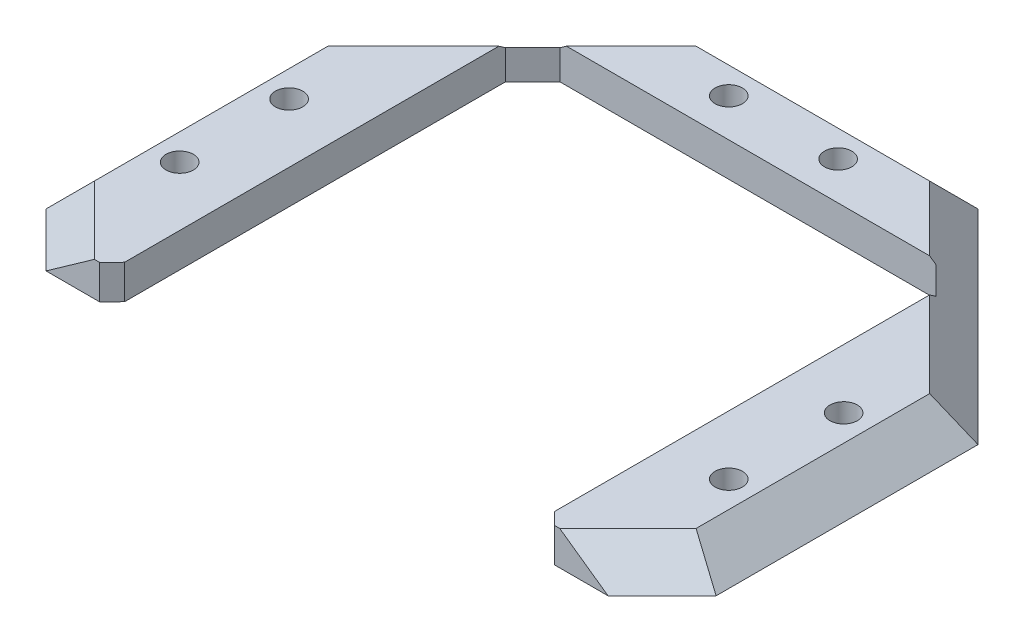
SolidWorks part; units mm, degrees
ref_plane "Front Plane" through (0, 0, 0) normal (0, 0, 1) x (1, 0, 0)
ref_plane "Top Plane" through (0, 0, 0) normal (0, 1, 0) x (1, 0, 0)
ref_plane "Right Plane" through (0, 0, 0) normal (1, 0, 0) x (0, 0, -1)
sketch "Sketch3" plane through (0, 0, 0) normal (0, 1, 0) x (1, 0, 0)
  line L0 (-11.0928, -75.2338) -> (-12.8828, -77.0838)
  line L1 (-12.8828, -77.0838) -> (-20.7428, -77.0838)
  line L2 (-20.7428, -77.0838) -> (-28.5928, -69.2338)
  line L3 (-28.5928, -69.2338) -> (-28.5928, -30.9338)
  line L4 (-28.5928, -30.9338) -> (-20.7428, -23.0838)
  line L5 (-20.7428, -23.0838) -> (-6.5928, -8.9338)
  line L6 (-6.5928, -8.9338) -> (1.2572, -1.0838)
  line L7 (1.2572, -1.0838) -> (39.5572, -1.0838)
  line L8 (39.5572, -1.0838) -> (47.4072, -8.9338)
  line L9 (47.4072, -8.9338) -> (69.4072, -30.9338)
  line L10 (69.4072, -30.9338) -> (69.4072, -69.2338)
  line L11 (69.4072, -69.2338) -> (61.5072, -77.1338)
  line L12 (61.5072, -77.1338) -> (53.6472, -77.1338)
  line L13 (53.6472, -77.1338) -> (51.9072, -75.3938)
  line L14 (51.9072, -75.3938) -> (51.9072, -19.559)
  line L15 (51.9072, -19.559) -> (47.9072, -15.559)
  line L16 (47.9072, -15.559) -> (-7.0928, -15.559)
  line L17 (-7.0928, -15.559) -> (-11.0928, -19.559)
  line L18 (-11.0928, -75.2338) -> (-11.0928, -19.559)
  dimension "D1" = 38.3
  dimension "D2" = 38.3
  dimension "D3" = 38.3
  dimension "D4" = 4
  dimension "D5" = 4
  dimension "D6" = 17.5
  dimension "D7" = 17.5
  dimension "D8" = 45
  dimension "D9" = 63
  dimension "D10" = 61.5748
extrude "Boss-Extrude1" add sketch "Sketch3" along normal blind 5
sketch "Sketch4" plane through (0, 5, 0) normal (0, 1, 0) x (1, 0, 0)
  line L0 (20.4072, -1015.559) -> (20.4072, 48984.441) construction
  line L1 (-7.0928, -15.559) -> (47.9072, -15.559) construction
  circle A0 centre (-19.7428, -58.5338) radius 2
  circle A1 centre (-19.7428, -42.5338) radius 2
  circle A2 centre (60.5572, -41.7338) radius 2
  circle A3 centre (60.5572, -58.5338) radius 2
  circle A4 centre (12.0072, -9.9838) radius 2
  circle A5 centre (28.0072, -9.9838) radius 2
  point P23 (20.4072, -15.559)
extrude "Cut-Extrude1" cut sketch "Sketch4" against normal blind 5
chamfer "Chamfer1" distance 5 angle 45 7 edges at (65.4572, 5, 73.1838) (-24.6678, 5, 73.1588) (-28.5928, 5, 50.0838) (-13.6678, 5, 16.0088) (20.4072, 5, 1.0838) (54.4822, 5, 16.0088) (69.4072, 5, 50.0838)
